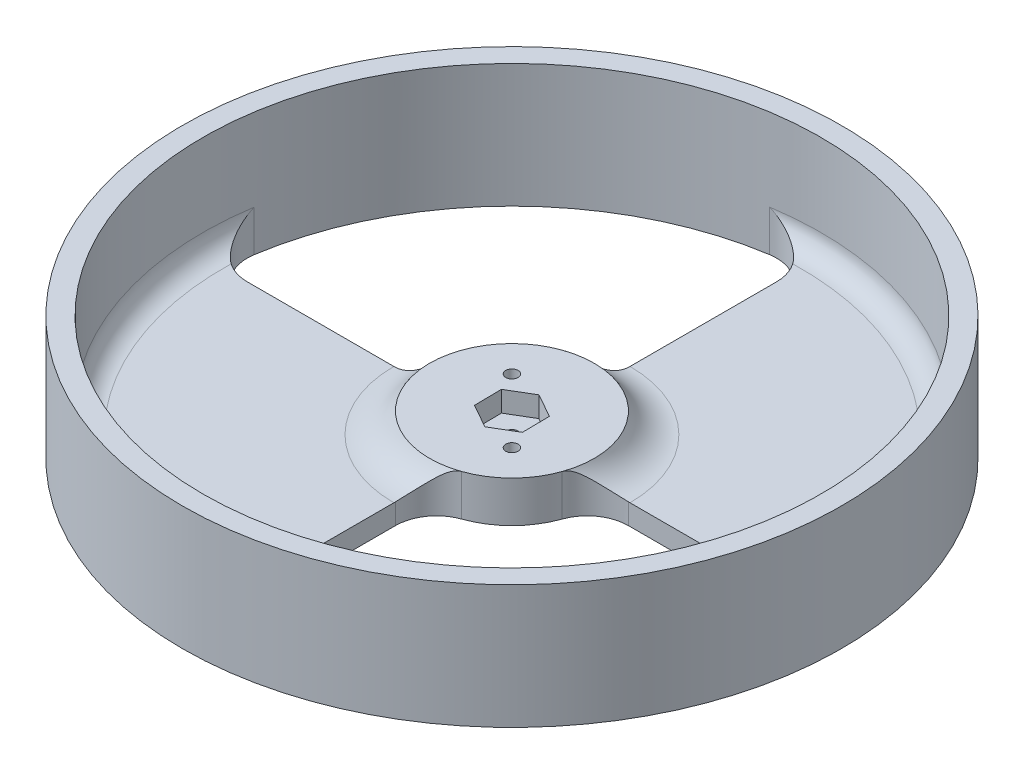
SolidWorks part; units mm, degrees
ref_plane "Front Plane" through (0, 0, 0) normal (0, 0, 1) x (1, 0, 0)
ref_plane "Top Plane" through (0, 0, 0) normal (0, 1, 0) x (1, 0, 0)
ref_plane "Right Plane" through (0, 0, 0) normal (1, 0, 0) x (0, 0, -1)
sketch "Sketch1" plane through (0, 0, 0) normal (0, 1, 0) x (1, 0, 0)
  line L1 (7.75, 7.75) -> (-7.75, 7.75) construction
  line L2 (7.75, 7.75) -> (7.75, -7.75) construction
  line L3 (7.75, -7.75) -> (-7.75, -7.75) construction
  line L4 (-7.75, 7.75) -> (-7.75, -7.75) construction
  line L5 (5.7936, -3.2431) -> (5.7054, 3.3959)
  line L6 (5.7054, 3.3959) -> (-0.0882, 6.6389)
  line L7 (-0.0882, 6.6389) -> (-5.7936, 3.2431)
  line L8 (-5.7936, 3.2431) -> (-5.7054, -3.3959)
  line L9 (-5.7054, -3.3959) -> (0.0882, -6.6389)
  line L10 (0.0882, -6.6389) -> (5.7936, -3.2431)
  line L29 (0, 75) -> (0, 20)
  line L30 (-20, 0) -> (-75, 0)
  line L31 (0, -75) -> (0, -20)
  line L32 (75, 0) -> (20, 0)
  circle A0 centre (0, 0) radius 5.75 construction
  circle A1 centre (-7.75, 7.75) radius 1.5
  circle A2 centre (0, 0) radius 20
  circle A3 centre (7.75, 7.75) radius 1.5
  circle A4 centre (7.75, -7.75) radius 1.5
  circle A5 centre (-7.75, -7.75) radius 1.5
  circle A6 centre (0, 0) radius 1.5
  circle A18 centre (0, 0) radius 80
  circle A19 centre (0, 0) radius 75
  point P22 (5.7495, 0.0764)
  dimension "D2" = 11.5
  dimension "D5" = 7.75
  dimension "D6" = 3
  dimension "D9" = 40
  dimension "D10" = 160
  dimension "D7" = 5
  dimension "D8" = 3
  dimension "D3" = 15.5
  dimension "D4" = 7.75
extrude "Boss-Extrude1" add sketch "Sketch1" along normal blind 10 contours A2 | A3 | A5 region at (13.7421, 0, -13.7421) region at (7.75, 0, -7.75) region at (-7.75, 0, 7.75)
extrude "Boss-Extrude2" add sketch "Sketch1<5>" along normal blind 5 contours L32 A19 L29 A2 | L30 A19 L31 A2 region at (33.618, 0, -33.618) region at (-33.618, 0, 33.618)
sketch "Sketch1<5>" plane through (0, 0, 0) normal (0, 1, 0) x (1, 0, 0) same geometry as "Sketch1"
extrude "Boss-Extrude3" add sketch "Sketch1<6>" along normal blind 30 contours A18 A19 region at (-77.7373, 0, 0)
sketch "Sketch1<6>" plane through (0, 0, 0) normal (0, 1, 0) x (1, 0, 0) same geometry as "Sketch1"
fillet "Fillet1" radius 5 2 edges at (-53.033, 5, 53.033) (53.033, 5, -53.033)
fillet "Fillet2" radius 10 8 edges at (0, 2.5, 20) (20, 2.5, 0) (0, 2.5, -20) (-20, 2.5, 0) (0, 5, -75) (75, 5, 0) (0, 5, 75) (-75, 5, 0)
fillet "Fillet3" radius 10 2 edges at (14.1421, 5, -14.1421) (-14.1421, 5, 14.1421)
sketch "Sketch2" plane through (0, 0, 0) normal (0, -1, 0) x (1, 0, 0)
  circle A0 centre (-7.75, -7.75) radius 3
  circle A1 centre (7.75, 7.75) radius 3
  dimension "D1" = 6
extrude "Cut-Extrude1" cut sketch "Sketch2" against normal blind 3
sketch "Sketch3" plane through (0, 0, 0) normal (0, -1, 0) x (1, 0, 0)
  line L1 (-6.0455, -3.3841) -> (-0.0921, -6.9276)
  line L2 (-0.0921, -6.9276) -> (5.9534, -3.5435)
  line L3 (5.9534, -3.5435) -> (6.0455, 3.3841)
  line L4 (6.0455, 3.3841) -> (0.0921, 6.9276)
  line L5 (0.0921, 6.9276) -> (-5.9534, 3.5435)
  line L6 (-5.9534, 3.5435) -> (-6.0455, -3.3841)
  circle A0 centre (0, 0) radius 6 construction
  circle A1 centre (0, 0) radius 1.5
  dimension "D1" = 3
extrude "Boss-Extrude4" add sketch "Sketch3" against normal blind 5
